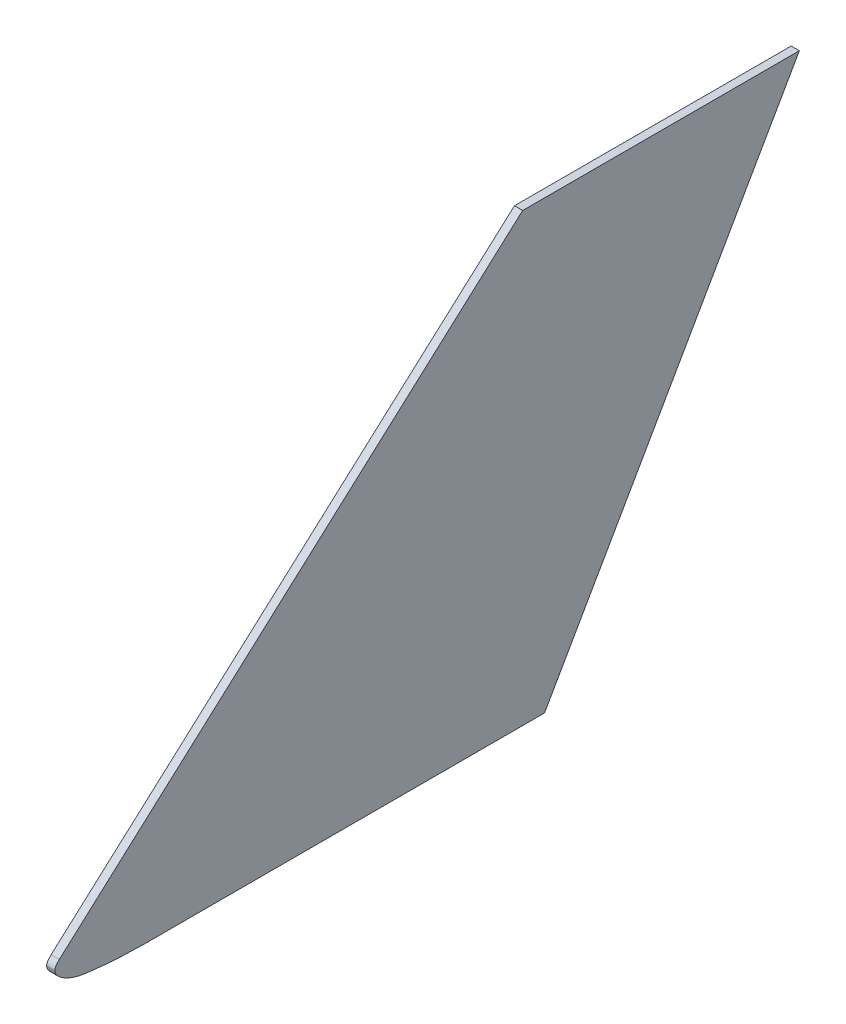
SolidWorks part; units mm, degrees
material "Winglet"
ref_plane "Front Plane" through (0, 0, 0) normal (0, 0, 1) x (1, 0, 0)
ref_plane "Top Plane" through (0, 0, 0) normal (0, 1, 0) x (1, 0, 0)
ref_plane "Right Plane" through (0, 0, 0) normal (1, 0, 0) x (0, 0, -1)
sketch "Sketch1" plane through (0, 0, 0) normal (1, 0, 0) x (0, 0, -1)
  line L0 (0, 0) -> (168.275, 0)
  line L1 (168.275, 0) -> (251.079, 145)
  line L2 (251.079, 145) -> (161.163, 145)
  line L3 (161.163, 145) -> (0, 0)
  dimension "D1" = 168.275
  dimension "D2" = 145
  dimension "D3" = 82.804
  dimension "D4" = 89.916
extrude "Boss-Extrude1" add sketch "Sketch1" along normal blind 2.667
sketch "Sketch2" plane through (0, 0, 0) normal (-1, 0, 0) x (0, 0, 1)
  line L0 (-58.3067, 0.4912) -> (-40.9692, 0) construction
  line L1 (-131.2701, 15.9151) -> (-125.292, 4.987) construction
  line L2 (-125.292, 4.987) -> (-96.5991, 2.5788) construction
  line L3 (-96.5991, 2.5788) -> (-58.3067, 0.4912) construction
  line L4 (-58.3067, 0.4912) -> (-40.9692, 0) construction
  line L5 (-131.2701, 15.9151) -> (-125.292, 4.987) construction
  line L6 (-125.292, 4.987) -> (-96.5991, 2.5788) construction
  line L7 (-96.5991, 2.5788) -> (-58.3067, 0.4912) construction
  line L8 (-38.2685, 0) -> (1.6038, -0.1367)
  line L10 (-10.613, 9.4828) -> (-7.657, 9.4828)
  line L11 (-7.657, 9.4828) -> (1.6038, -0.1367)
  line L12 (1.6038, -0.1367) -> (1.6562, -0.0616)
  parabola Q0 (-38.2685, 0) -> (-20.4792, 1.1041) focus (-33.037, 71.6752) apex (-27.8636, 0.3753) construction
  parabola Q1 (-38.2685, 0) -> (-20.4792, 1.1041) focus (-33.037, 71.6752) apex (-27.8636, 0.3753)
  spline S0 degree 3 poles (1959.6945, -278.8733) (-65.4856, 35.1493) (1.4913, -59.0914) (32.481, 107.5051) (-1921.3265, -575.3682) knots -0.350483 -0.350483 -0.350483 -0.350483 0.031804 0.571944 0.571944 0.571944 0.571944 only from (-20.4792, 1.1041) to (-9.0961, 6.9651) construction
  spline S2 degree 3 poles (-20.4792, 1.1041) (-19.7842, 1.1909) (-14.2944, 1.6921) (-9.1863, 4.9601) (-9.0961, 6.9651) knots 0 0 0 0 0.031804 0.095003 0.095003 0.095003 0.095003
  spline S3 degree 3 poles (-2008.549, 17.5649) (70.0647, -41.4969) (-3.8835, 12.9864) (-41.7081, 18.8012) (-257.6435, 25.7983) (-359.1009, -72.312) (-1887.8692, -939.2782) knots -0.389321 -0.389321 -0.389321 -0.389321 0.16879 0.324837 0.583849 4.625252 4.625252 4.625252 4.625252 only from (-9.0961, 6.9651) to (-131.2701, 15.9151) construction
  spline S4 degree 3 poles (-9.0961, 6.9651) (-9.0567, 7.842) (-9.65, 8.6866) (-10.613, 9.4828) knots 0.095003 0.095003 0.095003 0.095003 0.122644 0.122644 0.122644 0.122644
  line M4 (-168.275, 0) -> (0, 0)
extrude "Cut-Extrude1" cut sketch "Sketch2" against normal through all contours S2 Q1 M4 region at (0, 2.7245, -9.4152)
